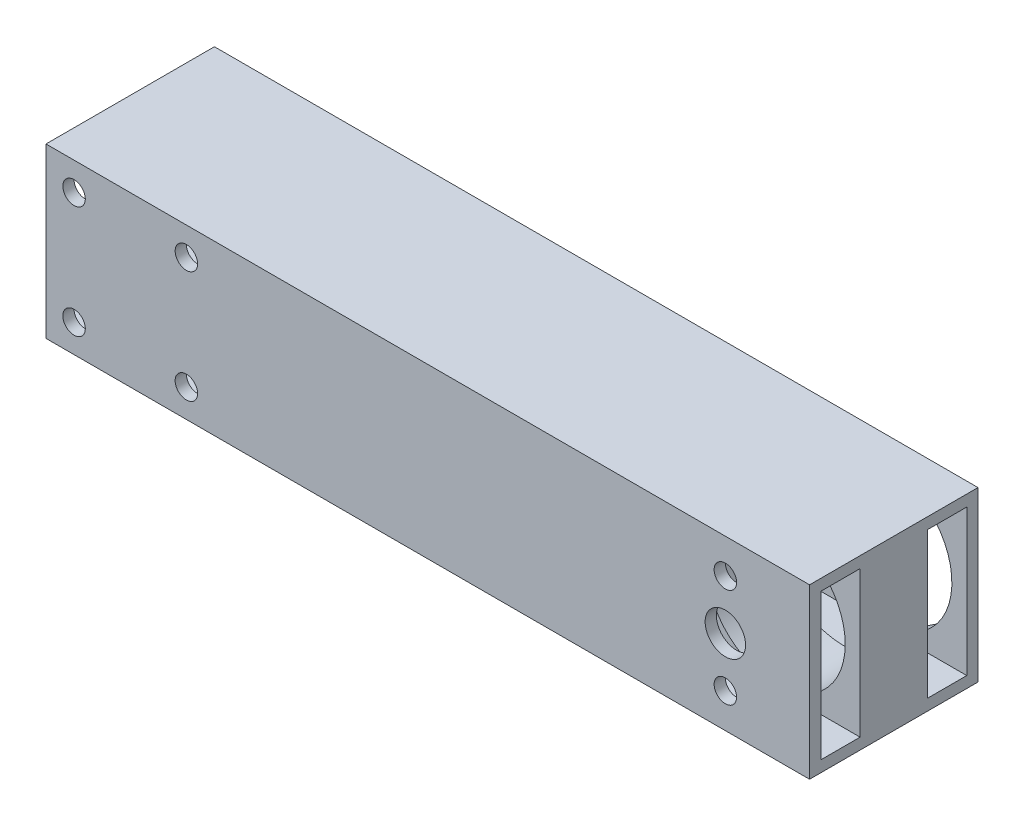
SolidWorks part; units mm, degrees
ref_plane "Front Plane" through (0, 0, 0) normal (0, 0, 1) x (1, 0, 0)
ref_plane "Top Plane" through (0, 0, 0) normal (0, 1, 0) x (1, 0, 0)
ref_plane "Right Plane" through (0, 0, 0) normal (1, 0, 0) x (0, 0, -1)
sketch "Sketch1" plane through (0, 0, 0) normal (1, 0, 0) x (0, 0, -1)
  line L1 (-15, -15) -> (15, -15)
  line L2 (-15, -15) -> (-15, 15)
  line L3 (-15, 15) -> (15, 15)
  line L4 (15, -15) -> (15, 15)
  line L5 (-15, -15) -> (15, 15) construction
  line L6 (-15, 15) -> (15, -15) construction
  line L11 (-5.1844, 5.1844) -> (5.1844, -5.1844) construction
  line L12 (-5.1844, -5.1844) -> (5.1844, 5.1844) construction
  line L13 (-13, 13) -> (-6, 13)
  line L14 (-13, 13) -> (-13, -13)
  line L15 (-13, -13) -> (-6, -13)
  line L16 (-6, 13) -> (-6, -13)
  line L17 (13, 13) -> (6, 13)
  line L18 (13, 13) -> (13, -13)
  line L19 (13, -13) -> (6, -13)
  line L20 (6, 13) -> (6, -13)
  point P0 (0, 0)
  point P7 (0, 0)
  dimension "D1" = 30
  dimension "D2" = 30
  dimension "D3" = 2
  dimension "D4" = 7
  dimension "D5" = 2
  dimension "D6" = 7
  dimension "D7" = 2
  dimension "D8" = 2
extrude "Boss-Extrude3" add sketch "Sketch1" along normal blind 90 and the other way blind 46
sketch "Sketch6" plane through (0, 0, -15) normal (0, 0, -1) x (-1, 0, 0)
  line L0 (-90, -15) -> (-90, 15) construction
  circle A0 centre (-75, 0) radius 12.35
  dimension "D2" = 24.7
  dimension "D1" = 15
extrude "Cut-Extrude5" cut sketch "Sketch6" against normal blind 23
sketch "Sketch8" plane through (0, 0, 15) normal (0, 0, 1) x (1, 0, 0)
  line L0 (90, 15) -> (90, -15) construction
  circle A0 centre (75, 0) radius 3.6
  circle A1 centre (75, 8.85) radius 2
  circle A2 centre (75, -8.85) radius 2
  dimension "D2" = 7.2
  dimension "D5" = 4
  dimension "D6" = 4
  dimension "D1" = 15
  dimension "D3" = 8.85
  dimension "D4" = 8.85
extrude "Cut-Extrude6" cut sketch "Sketch8" against normal blind 17
sketch "Sketch9" plane through (-46, 0, 0) normal (-1, 0, 0) x (0, 0, 1)
  line L0 (-6, 13) -> (6, 13)
  line L1 (-6, -13) -> (6, -13)
  line L2 (-6, 13) -> (-6, -13)
  line L3 (6, 13) -> (6, -13)
extrude "Cut-Extrude7" cut sketch "Sketch9" against normal blind 106
sketch "Sketch12" plane through (0, 0, 15) normal (0, 0, 1) x (1, 0, 0)
  line L0 (-46, 15) -> (90, 15) construction
  line L1 (-46, 15) -> (-46, -15) construction
  line L2 (-46, 15) -> (-16, 15) construction
  line L3 (-16, 15) -> (-16, -15) construction
  line L5 (-46, -15) -> (90, -15) construction
  circle A0 centre (-41, 10) radius 2
  circle A2 centre (-21, 10) radius 2
  circle A3 centre (-21, -10) radius 2
  circle A4 centre (-41, -10) radius 2
  dimension "D3" = 4
  dimension "D7" = 4
  dimension "D9" = 4
  dimension "D11" = 4
  dimension "D1" = 5
  dimension "D2" = 5
  dimension "D4" = 5
  dimension "D5" = 30
  dimension "D6" = 5
  dimension "D8" = 5
  dimension "D10" = 5
extrude "Cut-Extrude8" cut sketch "Sketch12" against normal blind 40 contours A0 | A2 | A3 | A4
